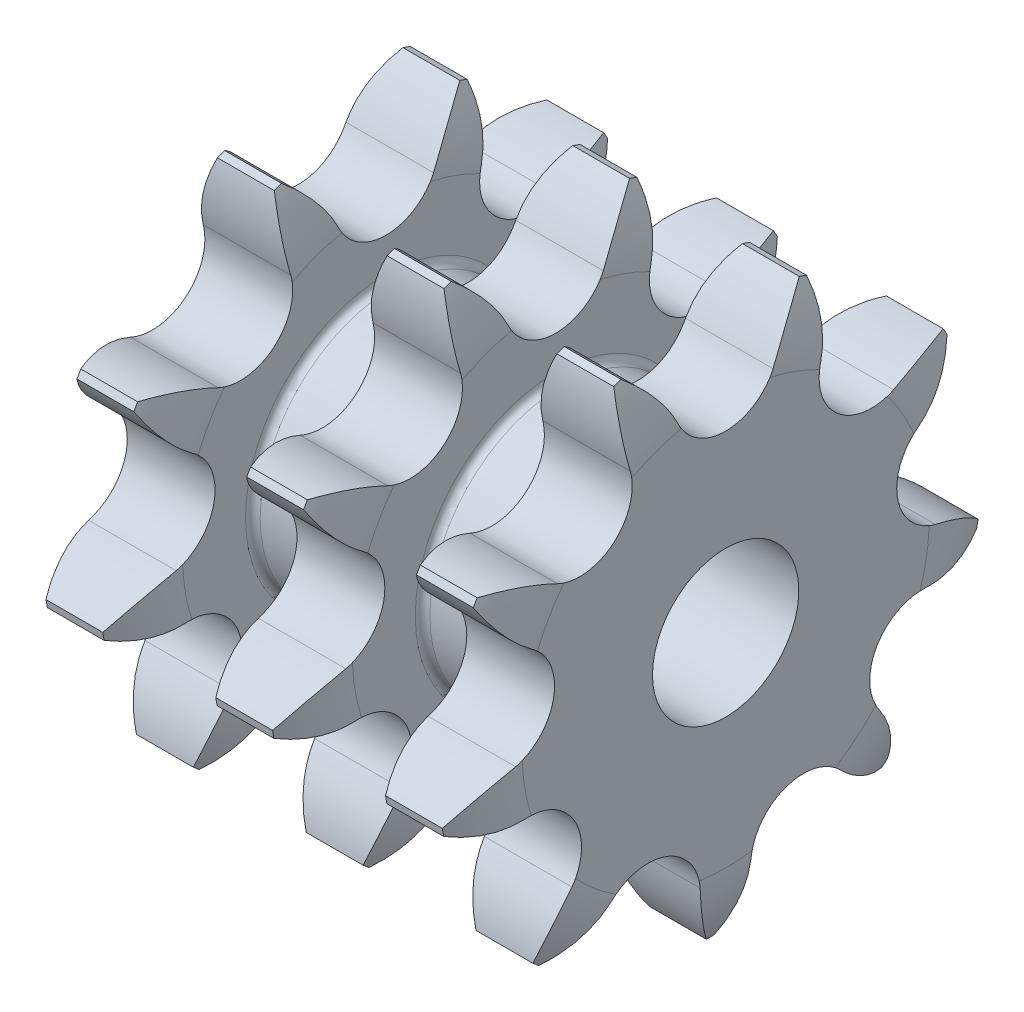
SolidWorks part; units mm, degrees
ref_plane "Plane1" through (0, 0, 0) normal (0, 0, 1) x (1, 0, 0)
ref_plane "Plane2" through (0, 0, 0) normal (0, 1, 0) x (1, 0, 0)
ref_plane "Plane3" through (0, 0, 0) normal (1, 0, 0) x (0, 0, -1)
sketch "Clipboard" plane through (0, 0, 0) normal (0, 1, 0) x (1, 0, 0)
  line L0 (0, 0) -> (12.5436, -1.9867)
  line L1 (-15, 0) -> (100, 0) construction
  line L2 (0, 0) -> (-0.8416, 0.9512)
  line L3 (0, 0) -> (-11.863, 4.5341)
  line L4 (0, 0) -> (3.0618, 0.4849)
  line L5 (0, 0) -> (-2.8109, -1.0484)
  line L6 (0, 0) -> (-29.0469, -19.598)
  line L7 (-0.8416, 0.9512) -> (35.5852, 8.6939)
  line L8 (-76.2, 38.1) -> (-75.2, 38.1)
  line L9 (-73.4259, 41.6592) -> (-72.8306, 41.7344)
  line L10 (-73.4741, 12.7512) -> (-59.5541, 12.7512)
  circle A0 centre (0, 0) radius 4.255
  circle A1 centre (0, 0) radius 10.8715
  circle A2 centre (0, 0) radius 25
  dimension "Num_teeth" = 9
  dimension "Thickness" = 35.04
  dimension "Fillet_rad" = 0.6
sketch "BasProSke" plane through (0, 0, 0) normal (0, 1, 0) x (1, 0, 0)
  line L0 (-10, 0) -> (60, 0) construction
  line L1 (0, 0) -> (0, 16.7129)
  line L2 (0, 0) -> (35.04, 0)
  line L3 (35.04, 0) -> (35.04, 16.7129)
  line L4 (33.77, 22.2487) -> (1.27, 22.2487)
  arc A0 (0, 16.7129) -> (1.27, 22.2487) centre (12.7, 16.7129) cw
  arc A1 (35.04, 16.7129) -> (33.77, 22.2487) centre (22.34, 16.7129) ccw
  dimension "D1" = 12.7
  dimension "Thickness" = 35.04
  dimension "Diameter" = 44.4973
  dimension "G1" = 1.27
revolve "Base-Revolve" add sketch "BasProSke" angle 360 about L0
sketch "GrvSke" plane through (0, 0, 0) normal (0, 1, 0) x (1, 0, 0)
  line L0 (7.2, 16.7129) -> (7.2, 11.5305)
  line L1 (7.8, 10.9305) -> (13.32, 10.9305)
  line L2 (13.92, 11.5305) -> (13.92, 16.7129)
  line L3 (5.93, 22.2487) -> (15.19, 22.2487)
  line L4 (10.56, 0) -> (10.56, 52.07) construction
  line L5 (-10, 0) -> (60, 0) construction
  line L6 (0, 0) -> (35.56, 0) construction
  arc A0 (13.92, 16.7129) -> (15.19, 22.2487) centre (26.62, 16.7129) cw
  arc A1 (7.2, 16.7129) -> (5.93, 22.2487) centre (-5.5, 16.7129) ccw
  arc A2 (7.2, 11.5305) -> (7.8, 10.9305) centre (7.8, 11.5305) ccw
  arc A3 (13.32, 10.9305) -> (13.92, 11.5305) centre (13.32, 11.5305) ccw
  dimension "D1" = 12.7
  dimension "Diameter" = 44.4973
  dimension "Fillet_rad" = 0.6
  dimension "G1" = 1.27
  dimension "Grv_width" = 6.72
revolve "Groove" cut sketch "GrvSke" angle 360 about L6
pattern_linear "Grooves" count 2 spacing 13.92 along (1, 0, 0) of "Groove"
sketch "TooCutSke" plane through (0, 0, 0) normal (1, 0, 0) x (0, 0, -1)
  line L0 (0, 18.6087) -> (3.8949, 16.7925) construction
  line L1 (0, 0) -> (0, 107) construction
  line L2 (0, 18.6087) -> (-10, 18.6087) construction
  line L3 (0, 18.6087) -> (-3.8949, 16.7925) construction
  arc A0 (3.8949, 16.7925) -> (7.8075, 21.3669) centre (14.0756, 12.0451) cw
  arc A1 (3.8949, 16.7925) -> (-3.8949, 16.7925) centre (0, 18.6087) cw
  arc A2 (-3.8949, 16.7925) -> (-7.8075, 21.3669) centre (-14.0756, 12.0451) ccw
  arc A3 (7.8075, 21.3669) -> (-7.8075, 21.3669) centre (0, 0) ccw
extrude "ToothCut" cut sketch "TooCutSke" along normal through all
pattern_circular "TeethCuts" count 9 every 40 about axis through (-10, 0, 0) along (1, 0, 0) of "ToothCut"
sketch "HubNeaOneSke" plane through (0, 0, 0) normal (-1, 0, 0) x (0, 0, 1)
  circle A0 centre (0, 0) radius 10.8715
  dimension "Diameter" = 21.743
extrude "HubNearOne" [suppressed] add sketch "HubNeaOneSke" along normal blind 2.2005
fillet "HubNearOneFillet" [suppressed] radius 0.6
sketch "HubNeaBotSke" plane through (0, 0, 0) normal (-1, 0, 0) x (0, 0, 1)
  circle A0 centre (0, 0) radius 10.8715
  dimension "Diameter" = 21.743
extrude "HubNearBoth" [suppressed] add sketch "HubNeaBotSke" along normal blind 1.1003
fillet "HubNearBothFillet" [suppressed] radius 0.6
ref_plane "FarPln" through (35.04, 0, 0) normal (1, 0, 0) x (0, 0, -1)
sketch "HubFarSke" plane through (35.04, 0, 0) normal (1, 0, 0) x (0, 0, -1)
  circle A0 centre (0, 0) radius 10.8715
  dimension "Diameter" = 21.743
extrude "HubFar" [suppressed] add sketch "HubFarSke" along normal blind 1.1003
fillet "HubFarFillet" [suppressed] radius 0.6
sketch "BorSke" plane through (0, 0, 0) normal (1, 0, 0) x (0, 0, -1)
  circle A0 centre (0, 0) radius 6
  dimension "Diameter" = 12
extrude "Bore" cut sketch "BorSke" along normal mid plane 74.481
sketch "KeySke" plane through (0, 0, 0) normal (1, 0, 0) x (0, 0, -1)
  line L0 (-1, 0) -> (-1, 7)
  line L1 (-1, 7) -> (1, 7)
  line L2 (1, 7) -> (1, 0)
  line L3 (0, 0) -> (0, 34) construction
  line L4 (-1, 0) -> (1, 0)
  dimension "Offset" = 7
  dimension "Width" = 2
extrude "Keyway" [suppressed] cut sketch "KeySke" along normal mid plane 74.481
pattern_circular "Keyway2" [suppressed] count 2 every 90 about axis through (-10, 0, 0) along (1, 0, 0) reverse direction yes
equation "' \"Pitch@Clipboard\" = 12.7"
equation "' \"Num_strands@Clipboard\" = 3"
equation "' \"Num_teeth@Clipboard\" = 9"
equation "' \"Hub_dia@Clipboard\" = 50"
equation "' \"Overall_len@Clipboard\" = 3"
equation "' \"Diameter@BorSke\" = 12"
equation "' \"T_dim@Clipboard\" = 1"
equation "' \"Width@KeySke\" = 2"
equation "' \"Dr@Clipboard\" = 8.51"
equation "' \"Face_width@Clipboard\" = 7.2"
equation "' \"Side_radius@Clipboard\" = 12.7"
equation "' \"Side_relief@Clipboard\" = 1.27"
equation "' \"Transv_pitch@Clipboard\" = 13.92"
equation "' \"Show_teeth@Clipboard\" = 9"
equation "' \"Fillet_rad@Clipboard\" = 0.6"
equation "' \"Plate_wid@Clipboard\" = 11.8"
equation "\"Num_teeth@Clipboard\" = int( \"Num_teeth@Clipboard\" )"
equation "\"Num_teeth@Clipboard\" = ((sgn( \"Num_teeth@Clipboard\" - 5.0)+1)*( \"Num_teeth@Clipboard\" - 5.0))/2 +5.0"
equation "\"Num_teeth@Clipboard\" = ((sgn( \"Num_teeth@Clipboard\" - 200.0)-1)*( \"Num_teeth@Clipboard\" - 200.0))/-2 +200.0"
equation "\"MHD@Clipboard\" = \"Pitch@Clipboard\" * (1.0 / tan(3.14159265 / \"Num_teeth@Clipboard\" )) - 1.05 * \"Plate_wid@Clipboard\" - 0.76"
equation "\"Thickness@Clipboard\"  = \"Face_width@Clipboard\" + (\"Num_strands@Clipboard\" - 1) * \"Transv_pitch@Clipboard\""
equation "\"OAL@Clipboard\" = \"Thickness@Clipboard\" + 2 * \"Fillet_rad@Clipboard\" + 1"
equation "\"MHD@Clipboard\" = ((sgn( \"MHD@Clipboard\" - \"Hub_dia@Clipboard\" )-1)*( \"MHD@Clipboard\" - \"Hub_dia@Clipboard\" ))/-2+ \"Hub_dia@Clipboard\""
equation "\"OAL@Clipboard\" = ((sgn( \"OAL@Clipboard\" - \"Overall_len@Clipboard\" )+1)*( \"OAL@Clipboard\" - \"Overall_len@Clipboard\" ))/2 + \"Overall_len@Clipboard\" + 0.0005"
equation "\"Num_teeth@TeethCuts\" = int( \"Show_teeth@Clipboard\" ) + 1"
equation "\"Num_teeth@TeethCuts\" = ((sgn( \"Num_teeth@TeethCuts\" - \"Num_teeth@Clipboard\" )-1)*( \"Num_teeth@TeethCuts\" - \"Num_teeth@Clipboard\" ))/-2+ \"Num_teeth@Clipboard\""
equation "\"Num_teeth@TeethCuts\" = ((sgn( \"Num_teeth@TeethCuts\" - 2.0)+1)*( \"Num_teeth@TeethCuts\" - 2.0))/2 +2.0"
equation "\"Angle@TeethCuts\" = 360.0 / \"Num_teeth@Clipboard\""
equation "\"Seat_radius@TooCutSke\" = ( \"Pitch@Clipboard\" / 2.0) / sin(3.14159265 / \"Num_teeth@Clipboard\" ) - \"Dr@Clipboard\" / 2.0 + \"Dr@Clipboard\" * 0.505"
equation "\"R1@TooCutSke\"  = \"Dr@Clipboard\" * 0.505"
equation "\"X@TooCutSke\" = 140.0 - (90.0 / \"Num_teeth@Clipboard\")"
equation "\"R2@TooCutSke\" = 0.12 * \"Dr@Clipboard\" * ( \"Num_teeth@Clipboard\" + 2.0)"
equation "\"Overcut@TooCutSke\" = 0.5 + 0.625 * \"Pitch@Clipboard\" - 0.5 * \"Dr@Clipboard\"  +  \"Pitch@Clipboard\" / 2.0 / sin(3.14159265 / \"Num_teeth@Clipboard\" )"
equation "\"Diameter@BasProSke\" = 2.0 * ( 0.625 * \"Pitch@Clipboard\" - 0.5 * \"Dr@Clipboard\"  +  \"Pitch@Clipboard\" / 2.0 / sin(3.14159265 / \"Num_teeth@Clipboard\" ))"
equation "\"Thickness@BasProSke\"  = \"Thickness@Clipboard\""
equation "\"G1@BasProSke\" =  \"Side_relief@Clipboard\""
equation "\"G2@BasProSke\" =  \"Side_relief@Clipboard\""
equation "\"D1@BasProSke\" =  \"Side_radius@Clipboard\""
equation "\"Diameter@GrvSke\" = \"Diameter@BasProSke\""
equation "\"G1@GrvSke\" = \"Side_relief@Clipboard\""
equation "\"D1@GrvSke\" = \"Side_radius@Clipboard\""
equation "\"Grv_diam@GrvSke\" =  \"Pitch@Clipboard\" * (1.0 / tan(3.14159265 / \"Num_teeth@Clipboard\" ))- 1.04 * \"Plate_wid@Clipboard\" - 0.76"
equation "\"Grv_width@GrvSke\" =  \"Transv_pitch@Clipboard\" - \"Face_width@Clipboard\""
equation "\"Offset@GrvSke\" = \"Grv_width@GrvSke\" / 2.0 + \"Face_width@Clipboard\""
equation "\"Fillet_rad@GrvSke\" = \"Fillet_rad@Clipboard\""
equation "\"Offset@Grooves\" = \"Transv_pitch@Clipboard\""
equation "\"Num_grvs@Grooves\" = \"Num_strands@Clipboard\""
equation "\"Num_grvs@Grooves\" = \"Num_grvs@Grooves\" - 1 * sgn( \"Num_grvs@Grooves\" -1)"
equation "\"Diameter@HubNeaOneSke\" = \"MHD@Clipboard\""
equation "\"Length@HubNearOne\" = \"OAL@Clipboard\" - \"Thickness@BasProSke\""
equation "\"Diameter@HubNeaBotSke\" = \"MHD@Clipboard\""
equation "\"Length@HubNearBoth\" = ( \"OAL@Clipboard\" - \"Thickness@BasProSke\" ) / 2.0"
equation "\"D1@HubNearOneFillet\" = \"Fillet_rad@Clipboard\""
equation "\"D1@HubNearBothFillet\" = \"Fillet_rad@Clipboard\""
equation "\"Thickness@FarPln\" = \"Thickness@BasProSke\""
equation "\"Diameter@HubFarSke\" = \"MHD@Clipboard\""
equation "\"Length@HubFar\" = ( \"OAL@Clipboard\" - \"Thickness@BasProSke\" ) / 2.0"
equation "\"D1@HubFarFillet\" = \"Fillet_rad@Clipboard\""
equation "\"D1@Bore\" = \"OAL@Clipboard\" * 2.0"
equation "\"D1@Keyway\" = \"OAL@Clipboard\" * 2.0"
equation "\"Offset@KeySke\" = \"T_dim@Clipboard\" + \"Diameter@BorSke\" / 2.0"
